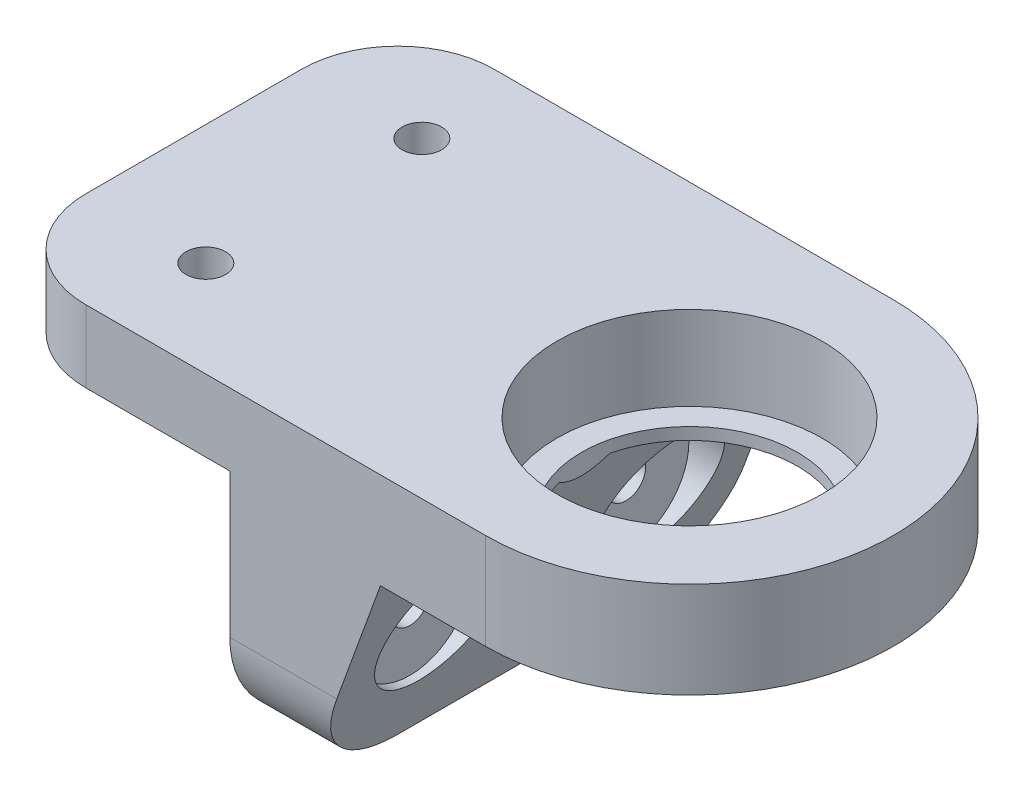
SolidWorks part; units mm, degrees
ref_plane "Plano frontal" through (0, 0, 0) normal (0, 0, 1) x (1, 0, 0)
ref_plane "Plano superior" through (0, 0, 0) normal (0, 1, 0) x (1, 0, 0)
ref_plane "Plano direito" through (0, 0, 0) normal (1, 0, 0) x (0, 0, -1)
sketch "Esboço1" plane through (0, 0, 0) normal (0, 0, 1) x (1, 0, 0)
  line L0 (0, 0) -> (6, 0)
  line L1 (49, 18) -> (49, 26)
  line L2 (49, 26) -> (-20, 26)
  line L3 (6, 0) -> (12.5515, 18)
  line L4 (-20, 26) -> (-20, 20)
  line L5 (0, 20) -> (0, 0)
  line L6 (-20, 20) -> (0, 20)
  line L7 (12.5515, 18) -> (49, 18)
  dimension "D1" = 20
  dimension "D2" = 8
  dimension "D3" = 6
  dimension "D4" = 20
  dimension "D5" = 6
  dimension "D6" = 20
extrude "Ressalto-extrusão1" add sketch "Esboço1" along normal blind 40
sketch "Esboço2" plane through (0, 18, 0) normal (0, -1, 0) x (1, 0, 0)
  line L0 (-20, 40) -> (-20, 0) construction
  line L1 (0, 20) -> (-20, 20) construction
  line L2 (49, 40) -> (49, 0) construction
  line L3 (0, 40) -> (0, 0) construction
  line L4 (21.3, 3) -> (-20, 3)
  line L6 (-20, 3) -> (-20, 0)
  line L7 (-20, 0) -> (49, 0)
  line L8 (49, 0) -> (49, 40)
  line L9 (49, 40) -> (-20, 40)
  line L10 (-20, 40) -> (-20, 37)
  line L11 (-20, 37) -> (21.3, 37)
  line L12 (0, 40) -> (0, 0) construction
  line L13 (-20, 40) -> (-20, 0) construction
  circle A0 centre (-10, 11) radius 1.65
  circle A1 centre (21.3, 20) radius 9
  arc A2 (21.3, 3) -> (21.3, 37) centre (21.3, 20) ccw
  circle A3 centre (-10, 29) radius 1.65
  point P16 (49, 20)
  dimension "D1" = 18
  dimension "D2" = 21.3
  dimension "D5" = 3.3
  dimension "D6" = 18
  dimension "D3" = 34
  dimension "D4" = 10
extrude "Corte-extrusão1" cut sketch "Esboço2" against normal through all both and the other way through all
sketch "Esboço3" plane through (0, 0, 0) normal (-1, 0, 0) x (0, 0, 1)
  line L0 (37, 0) -> (3, 0) construction
  line L2 (20, 20) -> (20, 0) construction
  line L5 (37, 20) -> (3, 20) construction
  line L6 (37, 20) -> (3, 20) construction
  circle A0 centre (29, 10) radius 1.65
  circle A1 centre (11, 10) radius 1.65
  dimension "D1" = 3.3
  dimension "D2" = 10
  dimension "D3" = 18
extrude "Corte-extrusão2" cut sketch "Esboço3" against normal through all
sketch "Esboço4" plane through (0, 26, 0) normal (0, 1, 0) x (1, 0, 0)
  circle A0 centre (21.3, -20) radius 11.05
  dimension "D1" = 22.1
extrude "Corte-extrusão3" cut sketch "Esboço4" against normal blind 7
sketch "Esboço7" plane through (0, 0, 0) normal (1, 0, 0) x (0, 0, -1)
  circle A0 centre (-29, 10) radius 5.25
  circle A1 centre (-11, 10) radius 5.25
  dimension "D1" = 10.5
extrude "Corte-extrusão5" cut sketch "Esboço7" along normal blind 10 from offset 7
fillet "Filete1" radius 8 4 edges at (3, 0, 3) (3, 0, 37) (-20, 23, 37) (-20, 23, 3)
sketch "Esboço8" plane through (0, 20, 0) normal (0, -1, 0) x (1, 0, 0)
  circle A0 centre (-10, 11) radius 5.25
  circle A1 centre (-10, 29) radius 5.25
  dimension "D1" = 10.5
extrude "Corte-extrusão6" cut sketch "Esboço8" against normal blind 1
extrude "Corte-extrusão7" cut sketch "Esboço7<2>" along normal blind 1
sketch "Esboço7<2>" plane through (0, 0, 0) normal (1, 0, 0) x (0, 0, -1) same geometry as "Esboço7"
